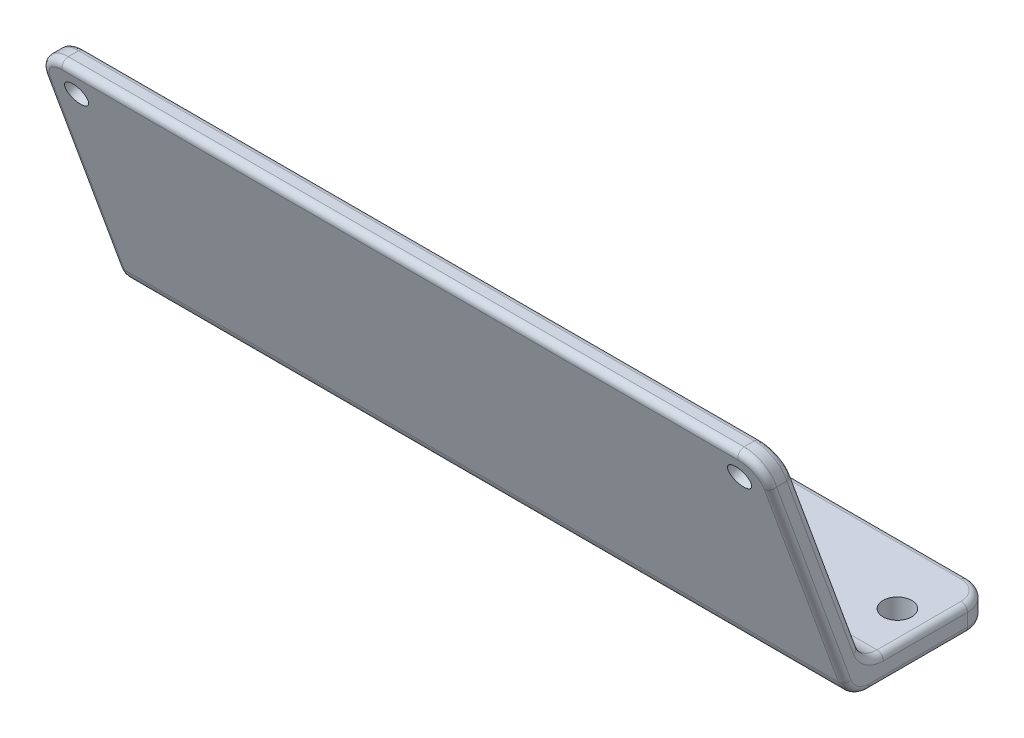
SolidWorks part; units mm, degrees
ref_plane "Front Plane" through (0, 0, 0) normal (0, 0, 1) x (1, 0, 0)
ref_plane "Top Plane" through (0, 0, 0) normal (0, 1, 0) x (1, 0, 0)
ref_plane "Right Plane" through (0, 0, 0) normal (1, 0, 0) x (0, 0, -1)
sketch "Sketch1" plane through (0, 0, 0) normal (0, 1, 0) x (1, 0, 0)
  line L0 (-57, 20) -> (-57, 0) construction
  line L1 (0, 0) -> (-114, 0)
  line L2 (0, 0) -> (0, 20)
  line L3 (0, 20) -> (-114, 20)
  line L4 (-114, 0) -> (-114, 20)
  circle A0 centre (-109, 10) radius 2.25
  circle A1 centre (-5, 10) radius 2.25
  point P11 (-114, 10)
  dimension "D1" = 4.5
  dimension "D2" = 104
  dimension "D4" = 10
  dimension "D3" = 5
extrude "Boss-Extrude1" add sketch "Sketch1" along normal blind 4
sketch "Sketch2" plane through (0, 0, 0) normal (1, 0, 0) x (0, 0, -1)
  line L4 (0, 4) -> (20, 4) construction
  line L6 (0, 4) -> (-12.739, 39)
  line L7 (-12.739, 39) -> (-16.4636, 39)
  line L8 (-16.4636, 39) -> (-2.2687, 0)
  line L9 (-2.2687, 0) -> (0, 0)
  line L10 (0, 0) -> (0, 4)
  dimension "D1" = 70
  dimension "D2" = 35
  dimension "3.5" = 3.5
extrude "Boss-Extrude2" add sketch "Sketch2" against normal through all
sketch "Sketch3" plane through (0, -0.7292, 2.0033) normal (0, -0.342, 0.9397) x (1, 0, 0)
  line L0 (-57, 42.2789) -> (-57, 0.776) construction
  line L1 (-114, 42.2789) -> (0, 42.2789) construction
  line L2 (-114, 0.776) -> (0, 0.776) construction
  line L3 (-114, 42.2789) -> (-114, 0.776) construction
  circle A0 centre (-109, 37.2789) radius 1.8
  circle A1 centre (-5, 37.2789) radius 1.8
  dimension "D1" = 3.6
  dimension "D2" = 5
  dimension "D3" = 5
extrude "Cut-Extrude1" cut sketch "Sketch3" against normal blind 4
fillet "Fillet1" radius 4 6 edges at (0, 2, -20) (-57, 0, 2.2687) (-114, 2, -20) (0, 39, 14.6013) (-114, 39, 14.6013) (-57, 4, 0)
fillet "Fillet2" radius 1 24 edges at (-112.8284, 37.8284, 12.3125) (-114, 20.816, 6.1205) (-114, 4.7234, -0.5065) (-114, 4, -9.4004) (-112.8284, 4, -18.8284) (-57, 4, -20) (-1.1716, 4, -18.8284) (0, 4, -9.4004) (0, 4.7234, -0.5065) (0, 20.816, 6.1205) (-1.1716, 37.8284, 12.3125) (-112.8284, 37.8284, 16.0372) (-114, 18.816, 9.1172) (-114, 0.7234, 1.7622) (-114, 0, -8.266) (-112.8284, 0, -18.8284) (-57, 0, -20) (-1.1716, 0, -18.8284) (0, 0, -8.266) (0, 0.7234, 1.7622) (0, 18.816, 9.1172) (-1.1716, 37.8284, 16.0372) (-57, 39, 12.739) (-57, 39, 16.4636)
